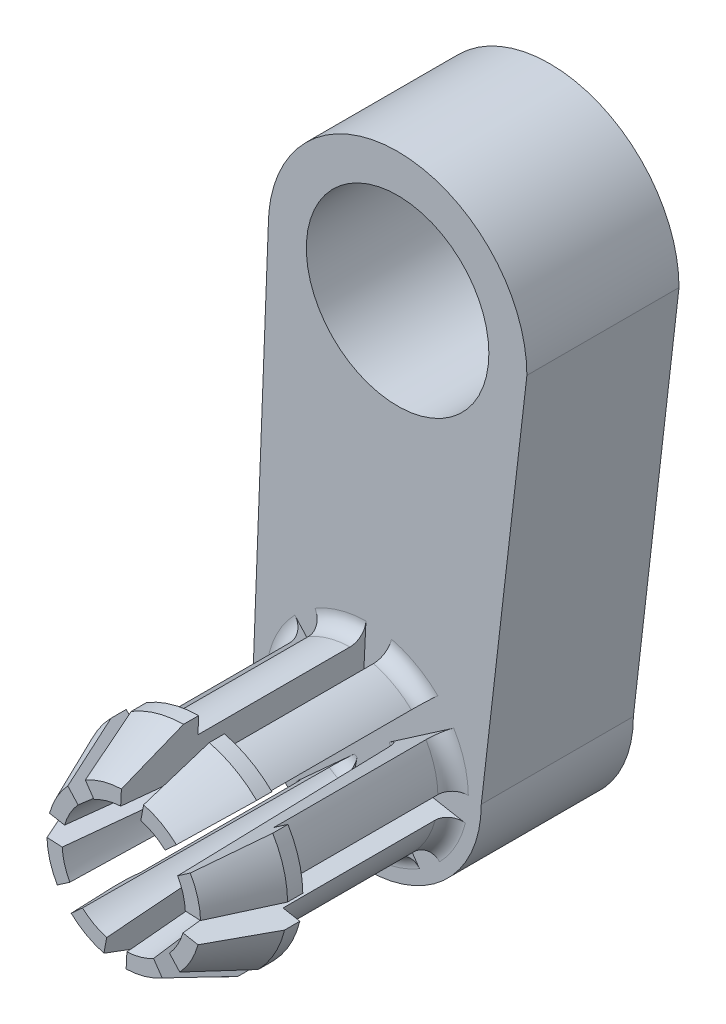
SolidWorks part; units mm, degrees
ref_plane "Front Plane" through (0, 0, 0) normal (0, 0, 1) x (1, 0, 0)
ref_plane "Top Plane" through (0, 0, 0) normal (0, 1, 0) x (1, 0, 0)
ref_plane "Right Plane" through (0, 0, 0) normal (1, 0, 0) x (0, 0, -1)
sketch "Sketch1" plane through (0, 0, 0) normal (0, 0, 1) x (1, 0, 0)
  line L1 (0, 0) -> (15.5, 0) construction
  line L2 (0, 0) -> (0, 7.5) construction
  line L6 (1, 33.423) -> (0, 7.5)
  line L7 (18, 33.423) -> (15, 7.5)
  arc A0 (0, 7.5) -> (15, 7.5) centre (7.5, 7.5) ccw
  arc A2 (17.7753, 31.4816) -> (1, 33.423) centre (9.5, 33.423) ccw
  circle A3 centre (9.5, 33.423) radius 6
  point P2 (1, 33.423)
  point P8 (18, 33.423)
  point P14 (15.5, 33.423)
  dimension "D1" = 15
  dimension "D2" = 12
  dimension "D5" = 17
  dimension "D3" = 26
  dimension "D4" = 2
extrude "Boss-Extrude1" add sketch "Sketch1" along normal blind 10 contours A0 region at (8.3425, 18.6741, 0)
sketch "Sketch3" plane through (0, 0, 10) normal (0, 0, 1) x (1, 0, 0)
  circle A0 centre (7.5, 7.5) radius 7.5
  arc A1 (0, 7.5) -> (15, 7.5) centre (7.5, 7.5) ccw construction
  point P6 (7.5, 7.5)
ref_plane "Plane1" through (6.5444, -0.7574, 0) normal (0.9934, -0.115, 0) x (0, 0, -1)
sketch "Sketch7" plane through (6.5444, -0.7574, 0) normal (0.9934, -0.115, 0) x (0, 0, -1)
  line L0 (-10, 8.3125) -> (-28.1597, 8.3125) construction
  line L2 (-10, 2.6625) -> (-21, 2.6625)
  line L3 (-10, 15.8125) -> (-10, 0.8125) construction
  line L4 (-21, 2.6625) -> (-21, 1.5425)
  line L5 (-21, 1.5425) -> (-22, 1.5425)
  line L6 (-22, 1.5425) -> (-26, 3.2625)
  line L7 (-26, 3.2625) -> (-26, 4.2625)
  line L8 (-26, 4.2625) -> (-10, 5.8625)
  line L9 (-10, 5.8625) -> (-10, 2.6625)
  dimension "D1" = 11
  dimension "D2" = 1.12
  dimension "D3" = 1
  dimension "D4" = 4
  dimension "D5" = 1
  dimension "D6" = 1.6
  dimension "D7" = 3.2
  dimension "D8" = 5.65
revolve "Revolve1" add sketch "Sketch7" angle 360 about L0
sketch "Sketch8" plane through (0, 0, 10) normal (0, 0, 1) x (1, 0, 0)
  line L0 (15.6692, 13.283) -> (13.0464, -9.381) construction
  line L1 (18, 33.423) -> (15, 7.5) construction
  line L2 (7.5, 7.5) -> (27.1149, 5.23) construction
  line L3 (7.546, 7.8973) -> (15.0043, 7.5375)
  line L4 (3.9817, -22.9014) -> (9.1071, 21.3866) construction
  line L5 (7.454, 7.1027) -> (14.7974, 5.7495)
  line L6 (15.0043, 7.5375) -> (14.7974, 5.7495)
  line L7 (7.546, 7.8973) -> (7.454, 7.1027)
  dimension "D1" = 1.8
  dimension "D2" = 0.8
extrude "Cut-Extrude1" cut sketch "Sketch8" along normal through all
ref_axis "Axis1" through (7.5, 7.5, 26) along (0, 0, -1)
pattern_circular "CirPattern1" count 8 over 360 about axis through (7.5, 7.5, 26) along (0, 0, -1) of "Cut-Extrude1"
fillet "Fillet1" radius 1 16 edges at (9.6407, 6.3084, 10) (9.8563, 8.1711, 10) (8.1711, 5.1437, 10) (6.3084, 5.3593, 10) (5.1437, 6.8289, 10) (5.3593, 8.6916, 10) (6.8289, 9.8563, 10) (8.6916, 9.6407, 10) (12.9339, 9.0477, 10) (10.2479, 12.4367, 10) (5.9523, 12.9339, 10) (2.5633, 10.2479, 10) (2.0661, 5.9523, 10) (4.7521, 2.5633, 10) (9.0477, 2.0661, 10) (12.4367, 4.7521, 10)
sketch "Sketch10" plane through (0, 0, 10) normal (0, 0, 1) x (1, 0, 0)
  line L2 (15, 7.5) -> (18, 33.423)
  line L3 (1, 33.423) -> (0, 7.5)
  line L4 (15, 7.5) -> (18, 33.423)
  line L5 (1, 33.423) -> (0, 7.5)
  circle A0 centre (9.5, 33.423) radius 8.5
  circle A1 centre (7.5, 7.5) radius 7.5
  arc A2 (0, 7.5) -> (15, 7.5) centre (7.5, 7.5) ccw
  arc A3 (18, 33.423) -> (1, 33.423) centre (9.5, 33.423) ccw
  arc A4 (0, 7.5) -> (15, 7.5) centre (7.5, 7.5) ccw
  arc A5 (18, 33.423) -> (1, 33.423) centre (9.5, 33.423) ccw
  line M38 (15, 7.5) -> (18, 33.423)
  line M40 (1, 33.423) -> (0, 7.5)
  dimension "D1" = 0
extrude "Cut-Extrude2" [suppressed] cut sketch "Sketch10" against normal through all both and the other way through all contours A1 A0 M38 M40
sketch "Sketch9" plane through (0, 0, 10) normal (0, 0, 1) x (1, 0, 0)
  line L0 (17.4571, 36.412) -> (26.9742, 11.0765)
  line L1 (3.5516, 27.3512) -> (9.0632, 21.9516)
  line L2 (9.5, 33.423) -> (7.5, 7.5) construction
  line L3 (24.6363, 5.9254) -> (10.1374, 0.479)
  line L5 (5.4846, 14.7241) -> (7.3388, 15.2414)
  circle A0 centre (9.5, 33.423) radius 8.5
  arc A1 (18, 33.423) -> (1, 33.423) centre (9.5, 33.423) ccw construction
  circle A3 centre (7.5, 7.5) radius 7.5 construction
  arc A5 (24.6363, 5.9254) -> (26.9742, 11.0765) centre (23.2297, 9.6699) ccw
  arc A6 (7.3388, 15.2414) -> (9.0632, 21.9516) centre (6.2639, 19.0943) ccw
  arc A7 (10.1374, 0.479) -> (5.4846, 14.7241) centre (7.5, 7.5) ccw
  arc M42 (0, 7.5) -> (15, 7.5) centre (7.5, 7.5) ccw
  dimension "D5" = 4
  dimension "20" = 25
  dimension "D2" = 90
  dimension "D3" = 50
  dimension "D4" = 60
extrude "Boss-Extrude2" [suppressed] add sketch "Sketch9" against normal up to surface (10 mm away) contours A0 L2 L3 A5 L0 M42 | L2 A0 L1 A6 L5 A7 | L2 A6 L5 A7 up to face at (15.5, 33.423, 0)
